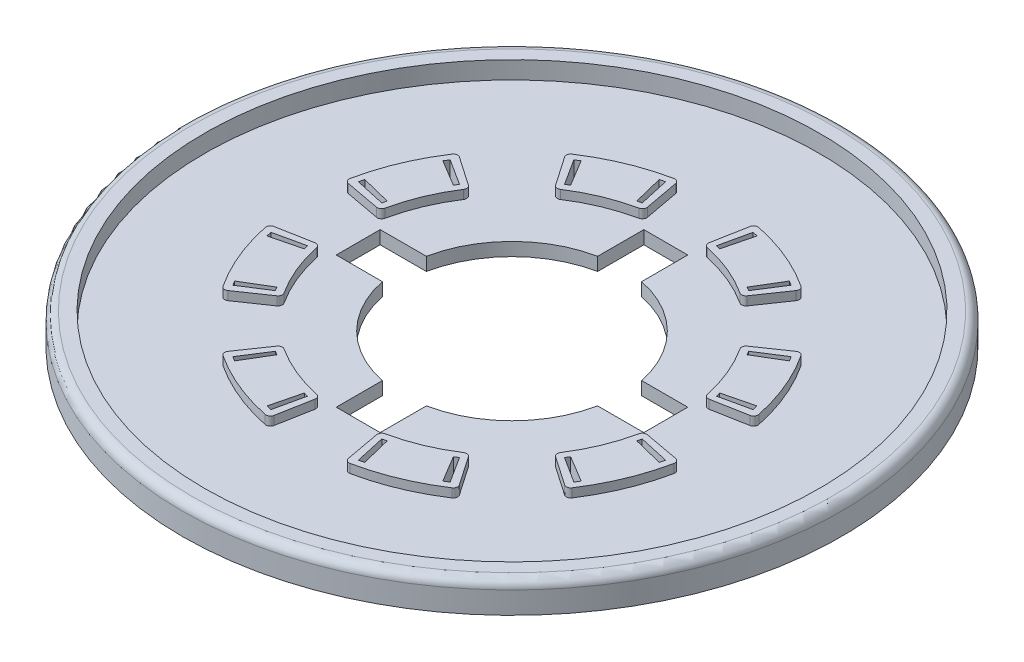
SolidWorks part; units mm, degrees
ref_plane "Alzado" through (0, 0, 0) normal (0, 0, 1) x (1, 0, 0)
ref_plane "Planta" through (0, 0, 0) normal (0, 1, 0) x (1, 0, 0)
ref_plane "Vista lateral" through (0, 0, 0) normal (1, 0, 0) x (0, 0, -1)
sketch "Croquis1" plane through (0, 0, 0) normal (0, 1, 0) x (1, 0, 0)
  circle A0 centre (0, 0) radius 75
  dimension "D1" = 150
extrude "Saliente-Extruir1" add sketch "Croquis1" along normal blind 3
sketch "Croquis3" plane through (0, 3, 0) normal (0, 1, 0) x (1, 0, 0)
  line L0 (-70, 0) -> (70, 0) construction
  line L1 (0, -70) -> (0, 70) construction
  line L3 (-49.4975, -49.4975) -> (49.4975, 49.4975) construction
  line L5 (-49.4975, 49.4975) -> (49.4975, -49.4975) construction
  circle A0 centre (0, 0) radius 75
  circle A1 centre (0, 0) radius 70
  dimension "D1" = 150
  dimension "D2" = 5
extrude "Saliente-Extruir2" add sketch "Croquis3" along normal blind 4
sketch "Croquis7" plane through (0, 3, 0) normal (0, 1, 0) x (1, 0, 0)
  line L0 (51.6188, -52.6795) -> (52.6795, -51.6188)
  line L9 (73.75, -0.75) -> (-73.75, -0.75)
  line L10 (73.75, -0.75) -> (73.75, 0.75)
  line L11 (73.75, 0.75) -> (-73.75, 0.75)
  line L12 (-73.75, -0.75) -> (-73.75, 0.75)
  line L13 (73.75, -0.75) -> (-73.75, 0.75) construction
  line L14 (73.75, 0.75) -> (-73.75, -0.75) construction
  line L15 (51.6188, -52.6795) -> (-52.6795, 51.6188)
  line L16 (-52.6795, 51.6188) -> (-51.6188, 52.6795)
  line L17 (52.6795, -51.6188) -> (-51.6188, 52.6795)
  line L18 (-0.75, -73.75) -> (0.75, -73.75)
  line L19 (-0.75, -73.75) -> (-0.75, 73.75)
  line L20 (-0.75, 73.75) -> (0.75, 73.75)
  line L21 (0.75, -73.75) -> (0.75, 73.75)
  line L22 (-52.6795, -51.6188) -> (-51.6188, -52.6795)
  line L23 (-52.6795, -51.6188) -> (51.6188, 52.6795)
  line L24 (51.6188, 52.6795) -> (52.6795, 51.6188)
  line L25 (-51.6188, -52.6795) -> (52.6795, 51.6188)
  line L26 (-73.75, 0.75) -> (-73.75, -0.75)
  line L27 (-73.75, 0.75) -> (73.75, 0.75)
  line L28 (73.75, 0.75) -> (73.75, -0.75)
  line L29 (-73.75, -0.75) -> (73.75, -0.75)
  point P0 (0, 0)
  point P25 (0, 0)
  dimension "D1" = 1.5
  dimension "D2" = 147.5
  dimension "D3" = 5
sketch "Croquis2" plane through (0, 0, 0) normal (0, -1, 0) x (1, 0, 0)
  line L0 (0, 0) -> (-75, 0) construction
  line L2 (0, 0) -> (-69.291, 28.7013) construction
  circle A0 centre (0, 0) radius 75 construction
  circle A1 centre (-55.4328, 22.961) radius 3.75
  circle A2 centre (-22.961, 55.4328) radius 3.75
  circle A3 centre (22.961, 55.4328) radius 3.75
  circle A4 centre (55.4328, 22.961) radius 3.75
  circle A5 centre (55.4328, -22.961) radius 3.75
  circle A6 centre (22.961, -55.4328) radius 3.75
  circle A7 centre (-22.961, -55.4328) radius 3.75
  circle A8 centre (-55.4328, -22.961) radius 3.75
  point P25 (0, 0)
  dimension "D1" = 7.5
  dimension "D2" = 60
  dimension "D4" = 22.5
  dimension "D3" = 8
extrude "Saliente-Extruir3" [suppressed] add sketch "Croquis7" along normal blind 1 contours L11 L19 L17 L15 | L11 L12 L9 L10 | L21 L20 L19 L18 | L23 L24 L25 L22 | L15 L16 L17 L0
extrude "Cortar-Extruir1" cut sketch "Croquis2" against normal blind 2
sketch "Croquis4" plane through (0, 0, 0) normal (0, -1, 0) x (1, 0, 0)
  circle A0 centre (0, 0) radius 25
  dimension "D1" = 50
extrude "Cortar-Extruir2" cut sketch "Croquis4" against normal blind 6
sketch "Croquis8" plane through (0, 3, 0) normal (0, 1, 0) x (1, 0, 0)
  line L0 (-45.7108, -8.472) -> (-37.8425, -7.0137)
  line L1 (-38.313, -26.3318) -> (-31.7182, -21.7993)
  line L2 (-38.313, 26.3318) -> (-31.7182, 21.7993)
  line L4 (-45.7108, 8.472) -> (-37.8425, 7.0137)
  line L20 (0, 0) -> (-75, 0) construction
  line L35 (-8.472, 45.7108) -> (-7.0137, 37.8425)
  line L36 (-26.3318, 38.313) -> (-21.7993, 31.7182)
  line L37 (26.3318, 38.313) -> (21.7993, 31.7182)
  line L38 (8.472, 45.7108) -> (7.0137, 37.8425)
  line L39 (45.7108, 8.472) -> (37.8425, 7.0137)
  line L40 (38.313, 26.3318) -> (31.7182, 21.7993)
  line L41 (38.313, -26.3318) -> (31.7182, -21.7993)
  line L42 (45.7108, -8.472) -> (37.8425, -7.0137)
  line L43 (8.472, -45.7108) -> (7.0137, -37.8425)
  line L44 (26.3318, -38.313) -> (21.7993, -31.7182)
  line L45 (-26.3318, -38.313) -> (-21.7993, -31.7182)
  line L46 (-8.472, -45.7108) -> (-7.0137, -37.8425)
  circle A0 centre (0, 0) radius 37.5 construction
  circle A1 centre (0, 0) radius 47.5 construction
  arc A2 (-36.6821, -7.7892) -> (-31.446, -20.4303) centre (0, 0) ccw
  arc A3 (-39.7155, -26.0562) -> (-46.5077, -9.6586) centre (0, 0) cw
  circle A52 centre (0, 0) radius 75 construction
  arc A53 (-38.313, -26.3318) -> (-39.7155, -26.0562) centre (-38.8794, -25.5077) cw
  arc A54 (-31.7182, -21.7993) -> (-31.446, -20.4303) centre (-32.2846, -20.9752) ccw
  arc A55 (-37.8425, -7.0137) -> (-36.6821, -7.7892) centre (-37.6603, -7.997) cw
  arc A56 (-45.7108, -8.472) -> (-46.5077, -9.6586) centre (-45.5285, -9.4552) ccw
  arc A57 (-46.5077, 9.6586) -> (-39.7155, 26.0562) centre (0, 0) cw
  arc A58 (-38.313, 26.3318) -> (-39.7155, 26.0562) centre (-38.8794, 25.5077) ccw
  arc A59 (-45.7108, 8.472) -> (-46.5077, 9.6586) centre (-45.5285, 9.4552) cw
  arc A60 (-31.7182, 21.7993) -> (-31.446, 20.4303) centre (-32.2846, 20.9752) cw
  arc A61 (-31.446, 20.4303) -> (-36.6821, 7.7892) centre (0, 0) ccw
  arc A62 (-37.8425, 7.0137) -> (-36.6821, 7.7892) centre (-37.6603, 7.997) ccw
  arc A63 (-26.0562, 39.7155) -> (-9.6586, 46.5077) centre (0, 0) cw
  arc A64 (-8.472, 45.7108) -> (-9.6586, 46.5077) centre (-9.4552, 45.5285) ccw
  arc A65 (-26.3318, 38.313) -> (-26.0562, 39.7155) centre (-25.5077, 38.8794) cw
  arc A66 (-7.0137, 37.8425) -> (-7.7892, 36.6821) centre (-7.997, 37.6603) cw
  arc A67 (-7.7892, 36.6821) -> (-20.4303, 31.446) centre (0, 0) ccw
  arc A68 (-21.7993, 31.7182) -> (-20.4303, 31.446) centre (-20.9752, 32.2846) ccw
  arc A69 (9.6586, 46.5077) -> (26.0562, 39.7155) centre (0, 0) cw
  arc A70 (26.3318, 38.313) -> (26.0562, 39.7155) centre (25.5077, 38.8794) ccw
  arc A71 (8.472, 45.7108) -> (9.6586, 46.5077) centre (9.4552, 45.5285) cw
  arc A72 (21.7993, 31.7182) -> (20.4303, 31.446) centre (20.9752, 32.2846) cw
  arc A73 (20.4303, 31.446) -> (7.7892, 36.6821) centre (0, 0) ccw
  arc A74 (7.0137, 37.8425) -> (7.7892, 36.6821) centre (7.997, 37.6603) ccw
  arc A75 (39.7155, 26.0562) -> (46.5077, 9.6586) centre (0, 0) cw
  arc A76 (45.7108, 8.472) -> (46.5077, 9.6586) centre (45.5285, 9.4552) ccw
  arc A77 (38.313, 26.3318) -> (39.7155, 26.0562) centre (38.8794, 25.5077) cw
  arc A78 (37.8425, 7.0137) -> (36.6821, 7.7892) centre (37.6603, 7.997) cw
  arc A79 (36.6821, 7.7892) -> (31.446, 20.4303) centre (0, 0) ccw
  arc A80 (31.7182, 21.7993) -> (31.446, 20.4303) centre (32.2846, 20.9752) ccw
  arc A81 (46.5077, -9.6586) -> (39.7155, -26.0562) centre (0, 0) cw
  arc A82 (38.313, -26.3318) -> (39.7155, -26.0562) centre (38.8794, -25.5077) ccw
  arc A83 (45.7108, -8.472) -> (46.5077, -9.6586) centre (45.5285, -9.4552) cw
  arc A84 (31.7182, -21.7993) -> (31.446, -20.4303) centre (32.2846, -20.9752) cw
  arc A85 (31.446, -20.4303) -> (36.6821, -7.7892) centre (0, 0) ccw
  arc A86 (37.8425, -7.0137) -> (36.6821, -7.7892) centre (37.6603, -7.997) ccw
  arc A87 (26.0562, -39.7155) -> (9.6586, -46.5077) centre (0, 0) cw
  arc A88 (8.472, -45.7108) -> (9.6586, -46.5077) centre (9.4552, -45.5285) ccw
  arc A89 (26.3318, -38.313) -> (26.0562, -39.7155) centre (25.5077, -38.8794) cw
  arc A90 (7.0137, -37.8425) -> (7.7892, -36.6821) centre (7.997, -37.6603) cw
  arc A91 (7.7892, -36.6821) -> (20.4303, -31.446) centre (0, 0) ccw
  arc A92 (21.7993, -31.7182) -> (20.4303, -31.446) centre (20.9752, -32.2846) ccw
  arc A93 (-9.6586, -46.5077) -> (-26.0562, -39.7155) centre (0, 0) cw
  arc A94 (-26.3318, -38.313) -> (-26.0562, -39.7155) centre (-25.5077, -38.8794) ccw
  arc A95 (-8.472, -45.7108) -> (-9.6586, -46.5077) centre (-9.4552, -45.5285) cw
  arc A96 (-21.7993, -31.7182) -> (-20.4303, -31.446) centre (-20.9752, -32.2846) cw
  arc A97 (-20.4303, -31.446) -> (-7.7892, -36.6821) centre (0, 0) ccw
  arc A98 (-7.0137, -37.8425) -> (-7.7892, -36.6821) centre (-7.997, -37.6603) ccw
  point P10 (-39.146, -26.9043)
  point P18 (-30.9047, -21.2402)
  point P21 (-36.8721, -6.8338)
  point P24 (-46.7046, -8.6562)
  point P45 (0, 0)
  point P113 (0, 0)
  point P115 (0, 0)
  dimension "D1" = 75
  dimension "D2" = 95
  dimension "D6" = 8
  dimension "D5" = 1
  dimension "D3" = 10.5
  dimension "D4" = 24
extrude "Saliente-Extruir4" add sketch "Croquis8" along normal blind 2
sketch "Croquis10" plane through (0, 5, 0) normal (0, 1, 0) x (1, 0, 0)
  line L0 (-44.9096, -9.9562) -> (-38.0755, -8.4411)
  line L1 (-44.6336, -11.1284) -> (-37.8415, -9.435)
  line L2 (-37.8425, -7.0137) -> (-45.7108, -8.472) construction
  line L3 (0, 0) -> (-43.8843, -18.1775) construction
  line L34 (-39.4297, 23.6918) -> (-33.4295, 20.0865)
  line L35 (-38.796, -24.7158) -> (-32.8923, -20.9547)
  line L36 (-39.4297, -23.6918) -> (-33.4295, -20.0865)
  line L37 (-38.796, 24.7158) -> (-32.8923, 20.9547)
  line L38 (-44.9096, 9.9562) -> (-38.0755, 8.4411)
  line L39 (-44.6336, 11.1284) -> (-37.8415, 9.435)
  line L40 (-11.1284, 44.6336) -> (-9.435, 37.8415)
  line L41 (-9.9562, 44.9096) -> (-8.4411, 38.0755)
  line L42 (-24.7158, 38.796) -> (-20.9547, 32.8923)
  line L43 (-23.6918, 39.4297) -> (-20.0865, 33.4295)
  line L44 (23.6918, 39.4297) -> (20.0865, 33.4295)
  line L45 (24.7158, 38.796) -> (20.9547, 32.8923)
  line L46 (9.9562, 44.9096) -> (8.4411, 38.0755)
  line L47 (11.1284, 44.6336) -> (9.435, 37.8415)
  line L48 (44.6336, 11.1284) -> (37.8415, 9.435)
  line L49 (44.9096, 9.9562) -> (38.0755, 8.4411)
  line L50 (38.796, 24.7158) -> (32.8923, 20.9547)
  line L51 (39.4297, 23.6918) -> (33.4295, 20.0865)
  line L52 (39.4297, -23.6918) -> (33.4295, -20.0865)
  line L53 (38.796, -24.7158) -> (32.8923, -20.9547)
  line L54 (44.9096, -9.9562) -> (38.0755, -8.4411)
  line L55 (44.6336, -11.1284) -> (37.8415, -9.435)
  line L56 (11.1284, -44.6336) -> (9.435, -37.8415)
  line L57 (9.9562, -44.9096) -> (8.4411, -38.0755)
  line L58 (24.7158, -38.796) -> (20.9547, -32.8923)
  line L59 (23.6918, -39.4297) -> (20.0865, -33.4295)
  line L60 (-23.6918, -39.4297) -> (-20.0865, -33.4295)
  line L61 (-24.7158, -38.796) -> (-20.9547, -32.8923)
  line L62 (-9.9562, -44.9096) -> (-8.4411, -38.0755)
  line L63 (-11.1284, -44.6336) -> (-9.435, -37.8415)
  circle A0 centre (0, 0) radius 39 construction
  circle A1 centre (0, 0) radius 46 construction
  arc A2 (-36.6821, -7.7892) -> (-31.446, -20.4303) centre (0, 0) ccw construction
  arc A3 (-46.5077, -9.6586) -> (-39.7155, -26.0562) centre (0, 0) ccw construction
  arc A4 (-38.0755, -8.4411) -> (-37.8415, -9.435) centre (0, 0) ccw
  arc A5 (-44.9096, -9.9562) -> (-44.6336, -11.1284) centre (0, 0) ccw
  arc A37 (-32.8923, -20.9547) -> (-33.4295, -20.0865) centre (0, 0) cw
  arc A38 (-38.796, -24.7158) -> (-39.4297, -23.6918) centre (0, 0) cw
  arc A39 (-38.796, 24.7158) -> (-39.4297, 23.6918) centre (0, 0) ccw
  arc A40 (-32.8923, 20.9547) -> (-33.4295, 20.0865) centre (0, 0) ccw
  arc A41 (-38.0755, 8.4411) -> (-37.8415, 9.435) centre (0, 0) cw
  arc A42 (-44.9096, 9.9562) -> (-44.6336, 11.1284) centre (0, 0) cw
  arc A43 (-9.9562, 44.9096) -> (-11.1284, 44.6336) centre (0, 0) ccw
  arc A44 (-8.4411, 38.0755) -> (-9.435, 37.8415) centre (0, 0) ccw
  arc A45 (-20.9547, 32.8923) -> (-20.0865, 33.4295) centre (0, 0) cw
  arc A46 (-24.7158, 38.796) -> (-23.6918, 39.4297) centre (0, 0) cw
  arc A47 (24.7158, 38.796) -> (23.6918, 39.4297) centre (0, 0) ccw
  arc A48 (20.9547, 32.8923) -> (20.0865, 33.4295) centre (0, 0) ccw
  arc A49 (8.4411, 38.0755) -> (9.435, 37.8415) centre (0, 0) cw
  arc A50 (9.9562, 44.9096) -> (11.1284, 44.6336) centre (0, 0) cw
  arc A51 (44.9096, 9.9562) -> (44.6336, 11.1284) centre (0, 0) ccw
  arc A52 (38.0755, 8.4411) -> (37.8415, 9.435) centre (0, 0) ccw
  arc A53 (32.8923, 20.9547) -> (33.4295, 20.0865) centre (0, 0) cw
  arc A54 (38.796, 24.7158) -> (39.4297, 23.6918) centre (0, 0) cw
  arc A55 (38.796, -24.7158) -> (39.4297, -23.6918) centre (0, 0) ccw
  arc A56 (32.8923, -20.9547) -> (33.4295, -20.0865) centre (0, 0) ccw
  arc A57 (38.0755, -8.4411) -> (37.8415, -9.435) centre (0, 0) cw
  arc A58 (44.9096, -9.9562) -> (44.6336, -11.1284) centre (0, 0) cw
  arc A59 (9.9562, -44.9096) -> (11.1284, -44.6336) centre (0, 0) ccw
  arc A60 (8.4411, -38.0755) -> (9.435, -37.8415) centre (0, 0) ccw
  arc A61 (20.9547, -32.8923) -> (20.0865, -33.4295) centre (0, 0) cw
  arc A62 (24.7158, -38.796) -> (23.6918, -39.4297) centre (0, 0) cw
  arc A63 (-24.7158, -38.796) -> (-23.6918, -39.4297) centre (0, 0) ccw
  arc A64 (-20.9547, -32.8923) -> (-20.0865, -33.4295) centre (0, 0) ccw
  arc A65 (-8.4411, -38.0755) -> (-9.435, -37.8415) centre (0, 0) cw
  arc A66 (-9.9562, -44.9096) -> (-11.1284, -44.6336) centre (0, 0) cw
  point P82 (0, 0)
  dimension "D1" = 1.5
  dimension "D2" = 1.5
  dimension "D3" = 2
  dimension "D4" = 1.5
extrude "Cortar-Extruir3" cut sketch "Croquis10" against normal blind 11
fillet "Redondeo1" radius 2 1 edges at (0, 7, 75)
sketch "Croquis11" plane through (0, 3, 0) normal (0, 1, 0) x (1, 0, 0)
  line L0 (-5, -35) -> (5, -35)
  line L1 (35, -5) -> (-35, -5)
  line L2 (35, -5) -> (35, 5)
  line L3 (35, 5) -> (-35, 5)
  line L4 (-35, -5) -> (-35, 5)
  line L5 (35, -5) -> (-35, 5) construction
  line L6 (35, 5) -> (-35, -5) construction
  line L7 (-5, -35) -> (-5, 35)
  line L8 (-5, 35) -> (5, 35)
  line L9 (5, -35) -> (5, 35)
  point P0 (0, 0)
  point P13 (0, 0)
  dimension "D1" = 70
  dimension "D2" = 10
  dimension "D3" = 2
extrude "Cortar-Extruir4" cut sketch "Croquis11" against normal blind 10 contours L4 L1 L3 | L9 L8 L7 | L2 L3 L1 | L0 L9 L7 region at (0, 3, 20) region at (-20, 3, 0) region at (20, 3, 0) region at (0, 3, -20)
